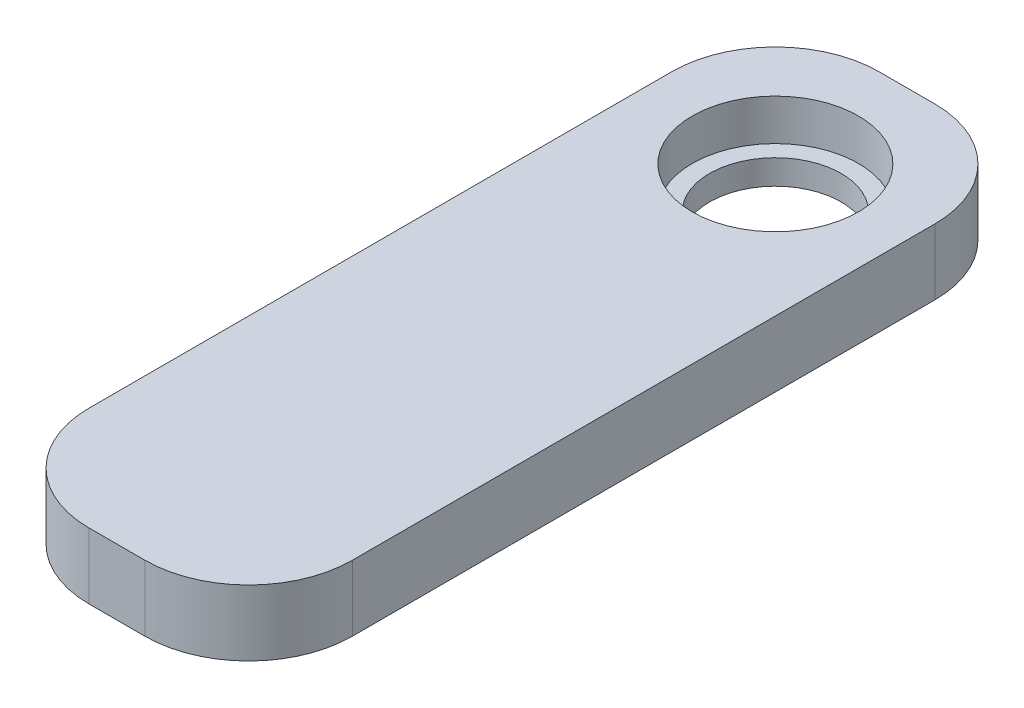
SolidWorks part; units mm, degrees
ref_plane "Front Plane" through (0, 0, 0) normal (0, 0, 1) x (1, 0, 0)
ref_plane "Top Plane" through (0, 0, 0) normal (0, 1, 0) x (1, 0, 0)
ref_plane "Right Plane" through (0, 0, 0) normal (1, 0, 0) x (0, 0, -1)
sketch "Sketch1" plane through (0, 0, 0) normal (0, 1, 0) x (1, 0, 0)
  line L1 (0, 0) -> (25.4, 0)
  line L2 (0, 0) -> (0, 76.2)
  line L3 (0, 76.2) -> (25.4, 76.2)
  line L4 (25.4, 0) -> (25.4, 76.2)
  dimension "D1" = 76.2
  dimension "D2" = 25.4
extrude "Boss-Extrude1" add sketch "Sketch1" along normal blind 6.35
sketch "Sketch5" plane through (0, 6.35, 0) normal (0, 1, 0) x (1, 0, 0)
  line L0 (0, 76.2) -> (0, 0) construction
  line L1 (25.4, 0) -> (25.4, 76.2) construction
  line L2 (25.4, 76.2) -> (0, 76.2) construction
  circle A0 centre (12.7, 63.5) radius 8.0169
  dimension "D3" = 16.0337
  dimension "D1" = 25.4
  dimension "D2" = 12.7
extrude "Cut-Extrude1" cut sketch "Sketch5" against normal blind 3.9688
sketch "Sketch6" plane through (0, 2.3812, 0) normal (0, 1, 0) x (1, 0, 0)
  circle A0 centre (12.7, 63.5) radius 6.35
  dimension "D1" = 12.7
extrude "Cut-Extrude2" cut sketch "Sketch6" against normal through all
sketch "Sketch7" plane through (0, 6.35, 0) normal (0, 1, 0) x (1, 0, 0)
  line L0 (25.4, 0) -> (25.4, 76.2) construction
  line L1 (0, 0) -> (25.4, 0) construction
  circle A0 centre (12.7, 6.35) radius 3.429
  dimension "D3" = 6.858
  dimension "D1" = 12.7
  dimension "D2" = 6.35
extrude "Cut-Extrude3" cut sketch "Sketch7" against normal blind 7.62
ref_axis "Axis1" through (12.7, 0, -6.35) along (0, 1, 0)
sketch "Sketch9" plane through (0, 6.35, 0) normal (0, 1, 0) x (1, 0, 0)
  line L1 (17.9251, 10.5572) -> (6.7267, 10.5572)
  line L2 (17.9251, 10.5572) -> (17.9251, 8.7376)
  line L3 (17.9251, 8.7376) -> (6.7267, 8.7376)
  line L4 (6.7267, 10.5572) -> (6.7267, 8.7376)
  dimension "D1" = 2.3876
extrude "Boss-Extrude2" add sketch "Sketch9" against normal through all
sketch "Sketch11" plane through (0, 0, 0) normal (0, -1, 0) x (1, 0, 0)
  line L1 (19.2592, -10.2867) -> (5.6226, -10.2867)
  line L2 (19.2592, -10.2867) -> (19.2592, -1.9718)
  line L3 (19.2592, -1.9718) -> (5.6226, -1.9718)
  line L4 (5.6226, -10.2867) -> (5.6226, -1.9718)
extrude "Boss-Extrude4" add sketch "Sketch11" along normal blind 1.27 from surface starting at face at (12.7, 6.35, -5.8293)
fillet "Fillet1" radius 10 4 edges at (0, 3.175, 0) (25.4, 3.175, 0) (0, 3.175, -76.2) (25.4, 3.175, -76.2)
